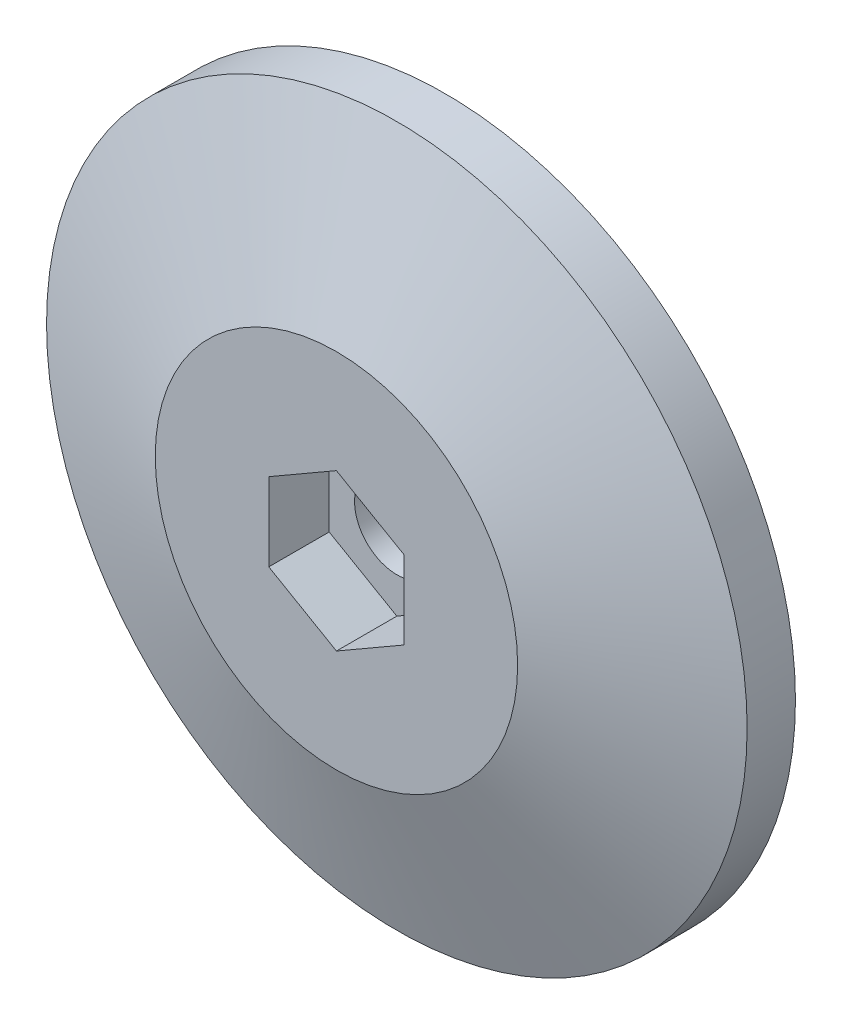
SolidWorks part; units mm, degrees
ref_plane "Спереди" through (0, 0, 0) normal (0, 0, 1) x (1, 0, 0)
ref_plane "Сверху" through (0, 0, 0) normal (0, 1, 0) x (1, 0, 0)
ref_plane "Справа" through (0, 0, 0) normal (1, 0, 0) x (0, 0, -1)
sketch "Эскиз1" plane through (0, 0, 0) normal (0, 0, 1) x (1, 0, 0)
  line L2 (0, 8.1134) -> (0, -19.5457) construction
  circle A2 centre (0, 0) radius 14.5
  circle A3 centre (0, 0) radius 1.75
  dimension "D4" = 29
  dimension "D5" = 3.5
extrude "Бобышка-Вытянуть1" add sketch "Эскиз1" along normal blind 2 contours A2
ref_plane "Плоскость1" through (0, 0, 4.5) normal (0, 0, 1) x (1, 0, 0)
sketch "Эскиз2" plane through (0, 0, 4.5) normal (0, 0, 1) x (1, 0, 0)
  line L1 (0, 3.2332) -> (-2.8, 1.6166)
  line L2 (-2.8, 1.6166) -> (-2.8, -1.6166)
  line L3 (-2.8, -1.6166) -> (0, -3.2332)
  line L4 (0, -3.2332) -> (2.8, -1.6166)
  line L5 (2.8, -1.6166) -> (2.8, 1.6166)
  line L6 (2.8, 1.6166) -> (0, 3.2332)
  circle A0 centre (0, 0) radius 7.5
  circle A1 centre (0, 0) radius 2.8 construction
  dimension "D1" = 15
  dimension "D2" = 5.6
loft "По сечениям1" add section face at (14.5, 0, 2) section "Эскиз2" connector at (10.3874, -10.1169, 2) connector at (4.9492, -5.6352, 4.5)
extrude "Вырез-Вытянуть2" cut sketch "Эскиз2<4>" against normal blind 2.5 contours L5 L6 L1 L2 L3 L4
sketch "Эскиз2<4>" plane through (0, 0, 4.5) normal (0, 0, 1) x (1, 0, 0) same geometry as "Эскиз2"
extrude "Вырез-Вытянуть1" cut sketch "Эскиз1<4>" along normal blind 2.8 contours A3
sketch "Эскиз1<4>" plane through (0, 0, 0) normal (0, 0, 1) x (1, 0, 0) same geometry as "Эскиз1"
